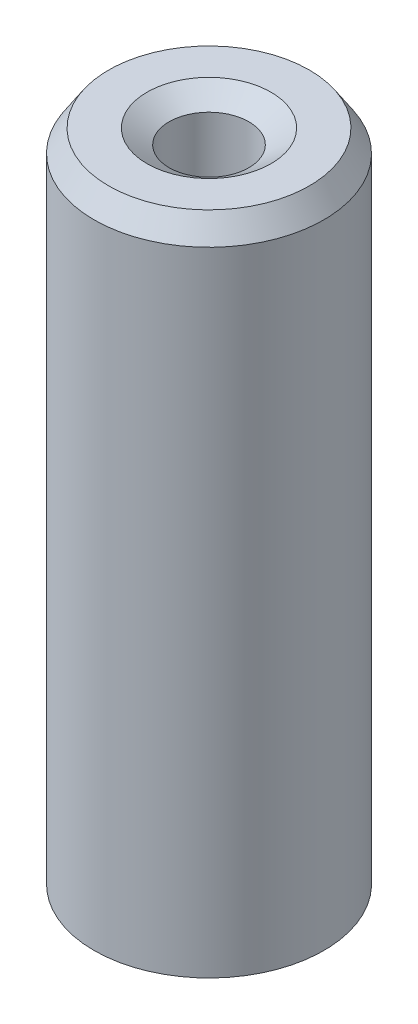
SolidWorks part; units mm, degrees
ref_plane "Front Plane" through (0, 0, 0) normal (0, 0, 1) x (1, 0, 0)
ref_plane "Top Plane" through (0, 0, 0) normal (0, 1, 0) x (1, 0, 0)
ref_plane "Right Plane" through (0, 0, 0) normal (1, 0, 0) x (0, 0, -1)
sketch "Sketch1" plane through (0, 0, 0) normal (0, 1, 0) x (1, 0, 0)
  circle A0 centre (0, 0) radius 15
  dimension "SLEEVE_OD" = 30
extrude "Boss-Extrude1" add sketch "Sketch1" along normal blind 87.3806
sketch "Sketch2" plane through (0, 0, 0) normal (0, 1, 0) x (1, 0, 0)
  circle A0 centre (0, 0) radius 5.2025
  dimension "BORE_D" = 10.4049
extrude "Cut-Extrude1" cut sketch "Sketch2" along normal through all
chamfer "Chamfer1" distance 2.8884 angle 33.296 4 edges at (0, 87.3806, 5.2025) (0, 0, 5.2025) (0, 0, 15) (0, 87.3806, 15) first distance on face at (0, 87.3806, 5.2025) first distance on face at (0, 0, 5.2025) first distance on face at (0, 87.3806, 15)
